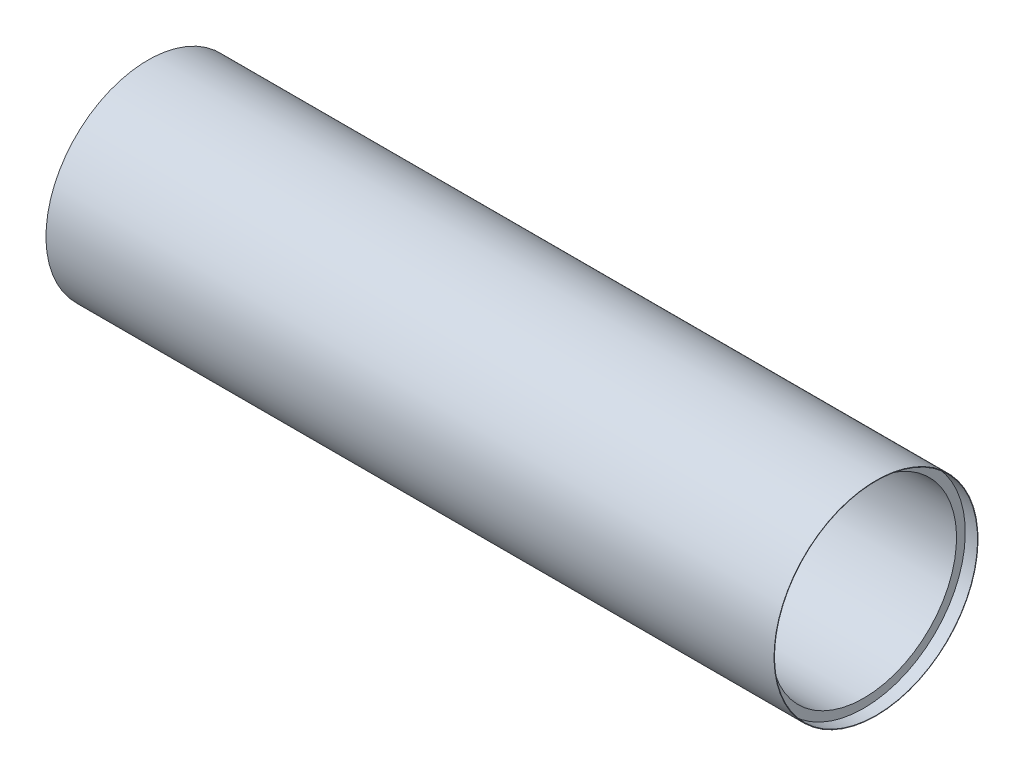
SolidWorks part; units mm, degrees
material "Carbon sandwich"
ref_plane "Front" through (0, 0, 0) normal (0, 0, 1) x (1, 0, 0)
ref_plane "Top" through (0, 0, 0) normal (0, 1, 0) x (1, 0, 0)
ref_plane "Right" through (0, 0, 0) normal (1, 0, 0) x (0, 0, -1)
sketch "Sketch1" plane through (0, 0, 0) normal (0, 0, 1) x (1, 0, 0)
  line L0 (39.1463, 83.9724) -> (49.3063, 83.9724)
  line L1 (49.3063, 83.9724) -> (49.3063, 76.7334)
  line L2 (49.3063, 76.7334) -> (631.0425, 76.7334)
  line L3 (631.0425, 76.7334) -> (631.0425, 83.9724)
  line L4 (631.0425, 83.9724) -> (641.2025, 83.9724)
  line L5 (641.2025, 83.9724) -> (641.2025, 84.3534)
  line L6 (641.2025, 84.3534) -> (39.1463, 84.3534)
  line L7 (39.1463, 84.3534) -> (39.1463, 83.9724)
  line L8 (0, 0) -> (134.0356, 0) construction
  dimension "D1" = 76.7334
  dimension "D2" = 0.381
  dimension "D3" = 10.16
  dimension "D4" = 10.16
  dimension "D5" = 581.7362
  dimension "D6" = 84.3534
  dimension "D7" = 0.381
revolve "Revolve1" add sketch "Sketch1" angle 360 about L8 region at (340.1744, 80.5497, 0)
ref_axis "Axis1" through (641.2025, 0, 0) along (-1, 0, 0)
